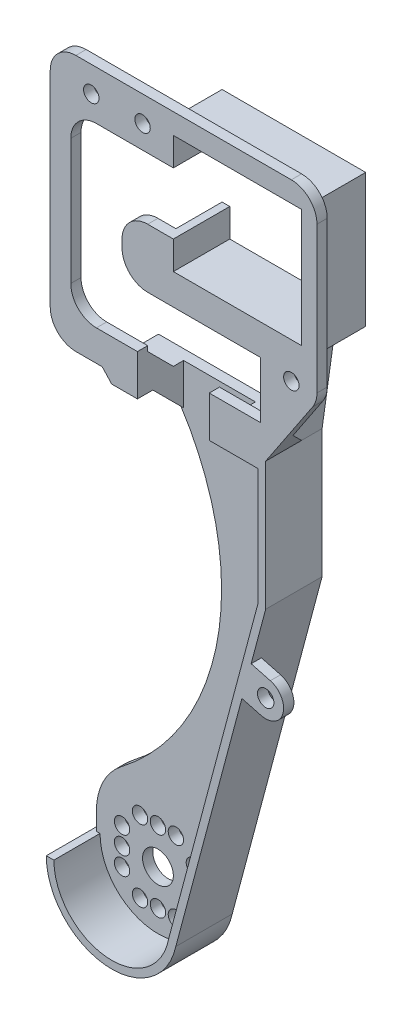
SolidWorks part; units mm, degrees
ref_plane "前视基准面" through (0, 0, 0) normal (0, 0, 1) x (1, 0, 0)
ref_plane "上视基准面" through (0, 0, 0) normal (0, 1, 0) x (1, 0, 0)
ref_plane "右视基准面" through (0, 0, 0) normal (1, 0, 0) x (0, 0, -1)
sketch "草图1" plane through (0, 0, 0) normal (1, 0, 0) x (0, 0, -1)
  line L0 (0, 0) -> (0, 98)
  line L1 (0, 98) -> (-9, 98)
  line L2 (-9, 98) -> (-9, 150)
  line L3 (-7, 150) -> (-7, 100)
  line L4 (-7, 100) -> (2, 100)
  line L5 (2, 100) -> (2, 0)
  line L6 (2, 0) -> (0, 0)
  line L7 (-7, 150) -> (-9, 150)
  point P9 (-2.5, 100)
  dimension "D1" = 2
  dimension "D2" = 2
  dimension "D3" = 2
  dimension "D4" = 9
  dimension "D5" = 52
  dimension "D6" = 100
extrude "凸台-拉伸1" add sketch "草图1" along normal blind 52
sketch "草图2" plane through (0, 0, 7) normal (0, 0, -1) x (-1, 0, 0)
  line L0 (-49, 146) -> (-49, 123)
  line L1 (-49, 123) -> (-24, 123)
  line L2 (-24, 123) -> (-24, 128.5)
  line L3 (-24, 128.5) -> (-14, 128.5)
  line L4 (-14, 128.5) -> (-14, 117)
  line L5 (-14, 117) -> (-41, 117)
  line L6 (-41, 117) -> (-41, 106)
  line L7 (-41, 106) -> (-31, 106)
  line L8 (-31, 106) -> (-31, 98)
  line L10 (-31, 98) -> (-17, 98)
  line L11 (-17, 98) -> (-17, 106)
  line L12 (-17, 106) -> (-4, 106)
  line L13 (-4, 106) -> (-4, 140.5)
  line L14 (-4, 140.5) -> (-24, 140.5)
  line L15 (-24, 140.5) -> (-24, 146)
  line L16 (-24, 146) -> (-49, 146)
  line L17 (-49, 134.5) -> (31.6365, 134.5) construction
  line L20 (-52, 100) -> (-52, 150) construction
  line L21 (-52, 98) -> (0, 98) construction
  point P20 (-14, 140.5)
  point P21 (-24, 125.75)
  dimension "D1" = 23
  dimension "D2" = 25
  dimension "D3" = 12
  dimension "D4" = 6
  dimension "D5" = 20
  dimension "D6" = 10
  dimension "D7" = 17
  dimension "D8" = 6
  dimension "D9" = 8
  dimension "D10" = 18
  dimension "D11" = 14
  dimension "D12" = 3
  dimension "D13" = 25
extrude "切除-拉伸1" cut sketch "草图2" against normal up to next and the other way blind 7
sketch "草图3" plane through (0, 0, -2) normal (0, 0, -1) x (-1, 0, 0)
  line L0 (-42, 75) -> (-22, 0)
  line L1 (-52, 100) -> (-52, 150) construction
  line L2 (-52, 0) -> (0, 0) construction
  line L3 (-22, 0) -> (-52, 0)
  line L4 (-52, 0) -> (-52, 115)
  line L5 (0, 0) -> (0, 100) construction
  line L6 (-15.5, 19) -> (-3.1235, 19) construction
  line L7 (-24.971, 12) -> (-2.1095, 12) construction
  line L8 (-15.5, 5) -> (-3.1235, 5) construction
  line L9 (-12, 19) -> (-12, -1.1388) construction
  line L10 (-5, 15.5) -> (-5, 8.3211) construction
  line L11 (-19, 15.5) -> (-19, 8.3211) construction
  line L12 (0, 100) -> (-10.1112, 100)
  line L13 (-17, 100) -> (0, 100) construction
  line L14 (0, 100) -> (0, 22.0483)
  line L15 (-42, 100) -> (-42, 75)
  line L17 (-42, 100) -> (-52, 115)
  line L18 (-52, 100) -> (0, 100) construction
  line L19 (-52, 100) -> (-31, 100) construction
  line L20 (0, 100) -> (0, 150) construction
  line L21 (-52, 150) -> (0, 150) construction
  circle A0 centre (-15.5, 19) radius 1.5
  circle A1 centre (-12, 19) radius 1.5
  circle A2 centre (-8.5, 19) radius 1.5
  circle A3 centre (-8.5, 5) radius 1.5
  circle A4 centre (-12, 5) radius 1.5
  circle A5 centre (-15.5, 5) radius 1.5
  circle A6 centre (-5, 15.5) radius 1.5
  circle A7 centre (-5, 12) radius 1.5
  circle A8 centre (-5, 8.5) radius 1.5
  circle A9 centre (-19, 8.5) radius 1.5
  circle A10 centre (-19, 12) radius 1.5
  circle A11 centre (-19, 15.5) radius 1.5
  arc A12 (-10.1112, 100) -> (0, 22.0483) centre (25.596, 65) ccw
  circle A13 centre (-8, 145) radius 1.5
  circle A14 centre (-47, 116) radius 1.5
  circle A15 centre (-18, 145) radius 1.5
  circle A16 centre (-12, 12) radius 3
  point P66 (-44.2056, 100)
  dimension "D4" = 3
  dimension "D5" = 3
  dimension "D6" = 3
  dimension "D8" = 3.5
  dimension "D9" = 3.5
  dimension "D10" = 3
  dimension "D11" = 3
  dimension "D12" = 3
  dimension "D13" = 14
  dimension "D16" = 100
  dimension "D20" = 3
  dimension "D21" = 3
  dimension "D22" = 8
  dimension "D24" = 5
  dimension "D26" = 3
  dimension "D27" = 10
  dimension "D29" = 6
  dimension "D1" = 22
  dimension "D2" = 3.5
  dimension "D3" = 3.5
  dimension "D7" = 14
  dimension "D14" = 12
  dimension "D15" = 12
  dimension "D17" = 65
  dimension "D18" = 25
  dimension "D19" = 15
  dimension "D23" = 5
  dimension "D25" = 16
  dimension "D28" = 5
  dimension "D30" = 10
extrude "切除-拉伸2" cut sketch "草图3" against normal through all
fillet "圆角1" radius 5 8 edges at (4, 106, 8) (4, 140.5, 8) (14, 117, 8) (14, 128.5, 8) (52, 150, 8) (52, 115, 8) (0, 100, 8) (0, 150, 8)
chamfer "倒角1" distance 5 angle 45 2 edges at (13.5556, 100, 7) (36.5, 100, 7)
fillet "圆角2" radius 12.5 3 edges at (22, 0, -1) (0, 0, -1) (0, 22.0483, -1)
sketch "草图4" plane through (0, 0, 7) normal (0, 0, -1) x (-1, 0, 0)
  line L0 (-24, 128.5) -> (-24, 123)
  line L1 (-24, 123) -> (-49, 123)
  line L2 (-49, 123) -> (-49, 146)
  line L3 (-49, 146) -> (-24, 146)
  line L4 (-24, 146) -> (-24, 140.5)
  line L5 (-24, 140.5) -> (-22.5, 140.5)
  line L6 (-9, 140.5) -> (-24, 140.5) construction
  line L7 (-22.5, 140.5) -> (-22.5, 147.5)
  line L8 (-22.5, 147.5) -> (-50.5, 147.5)
  line L9 (-50.5, 147.5) -> (-50.5, 121.5)
  line L10 (-50.5, 121.5) -> (-45, 121.5)
  line L11 (-22.5, 121.5) -> (-22.5, 128.5)
  line L12 (-24, 128.5) -> (-19, 128.5) construction
  line L13 (-22.5, 128.5) -> (-24, 128.5)
  line L14 (-42, 100) -> (-45, 121.5)
  line L15 (-42, 100) -> (-40.4855, 100)
  line L16 (-31, 100) -> (-42, 100) construction
  line L17 (-40.4855, 100) -> (-43.4855, 121.5)
  line L19 (-43.4855, 121.5) -> (-22.5, 121.5)
  dimension "D1" = 1.5
  dimension "D2" = 1.5
  dimension "D3" = 1.5
  dimension "D4" = 1.5
  dimension "D5" = 1.5
  dimension "D6" = 5.5
extrude "凸台-拉伸2" add sketch "草图4" along normal blind 9
sketch "草图6" plane through (0, 0, 0) normal (0, 0, 1) x (1, 0, 0)
  line L0 (42, 98) -> (42, 75)
  line L1 (42, 75) -> (24.4745, 9.2792)
  line L2 (23.1066, 9.9714) -> (40.5, 75.1966)
  line L3 (40.5, 75.1966) -> (40.5, 98)
  line L4 (42, 98) -> (31, 98) construction
  line L5 (40.5, 98) -> (42, 98)
  line L6 (0.7096, 12) -> (-0.7677, 12)
  arc A1 (-0.7677, 12) -> (24.4745, 9.2792) centre (12, 12) ccw
  arc A2 (0.7096, 12) -> (23.1066, 9.9714) centre (12, 12) ccw
  dimension "D1" = 1.5
  dimension "D2" = 1.5
extrude "凸台-拉伸3" add sketch "草图6" along normal blind 9 and the other way blind 2
chamfer "倒角3" distance 6 angle 45 2 edges at (14.4837, 98, 0) (35.75, 98, 0)
sketch "草图7" plane through (0, 0, -2) normal (0, 0, -1) x (-1, 0, 0)
  line L0 (-39.1674, 64.3777) -> (-42.9018, 63.3818)
  line L1 (-24.4745, 9.2792) -> (-42, 75) construction
  line L2 (-37.3637, 57.614) -> (-41.0982, 56.6182)
  line L3 (-39.1674, 64.3777) -> (-37.3637, 57.614)
  arc A0 (-42.9018, 63.3818) -> (-41.0982, 56.6182) centre (-42, 60) ccw
  circle A1 centre (-42, 60) radius 1.6
  dimension "D1" = 3.2
  dimension "D2" = 7
  dimension "D4" = 42
  dimension "D3" = 60
extrude "凸台-拉伸4" add sketch "草图7" along normal blind 2 from offset 11 offset against normal yes
